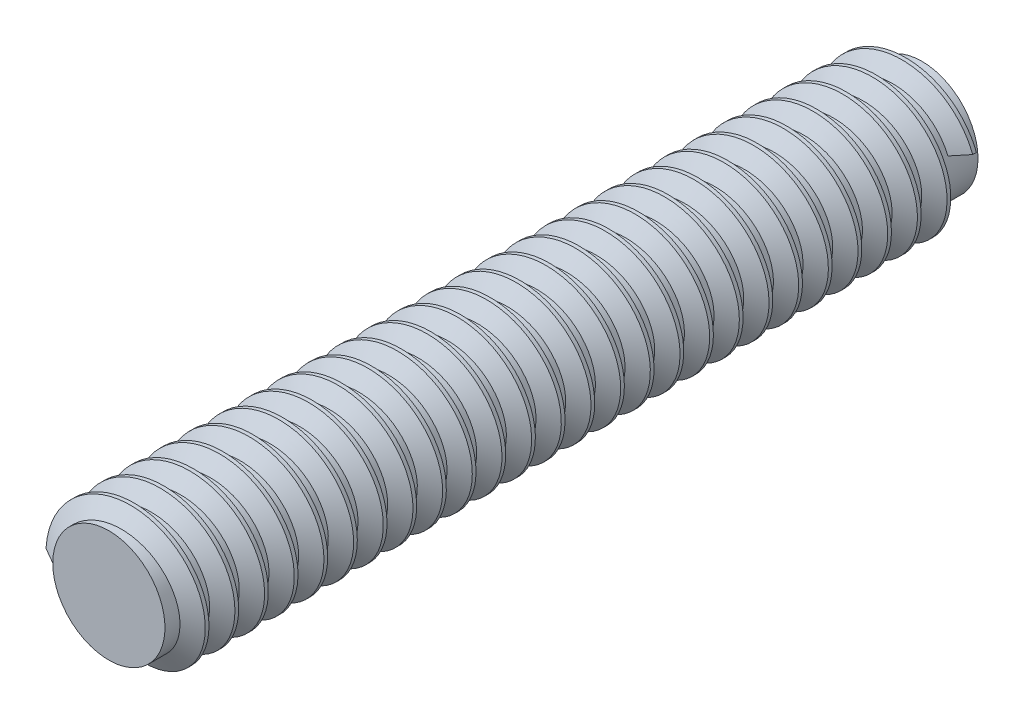
SolidWorks part; units mm, degrees
ref_plane "Front Plane" through (0, 0, 0) normal (0, 0, 1) x (1, 0, 0)
ref_plane "Top Plane" through (0, 0, 0) normal (0, 1, 0) x (1, 0, 0)
ref_plane "Right Plane" through (0, 0, 0) normal (1, 0, 0) x (0, 0, -1)
sketch "Sketch1" plane through (0, 0, 0) normal (0, 0, 1) x (1, 0, 0)
  circle A0 centre (0, 0) radius 2
  dimension "D1" = 4
extrude "Boss-Extrude1" add sketch "Sketch1" along normal blind 29
thread "Thread2" pitch 1.0583 method extrude profile "Thread Profile2" start angle 0, offset 0, length 28, pitch 1.0583, diameter 4
ref_plane "Plane2" through (-2, 0, 29) normal (0, -1, 0) x (-1, 0, 0)
sketch "Thread Profile2" plane through (-2, 0, 29) normal (0, -1, 0) x (-1, 0, 0)
  line L0 (0, 0) -> (0, 1.0583) construction
  line L1 (0, 0) -> (0.5728, 0.3307)
  line L2 (0.5728, 0.3307) -> (0.5728, 0.463)
  line L3 (0.5728, 0.463) -> (0, 0.7937)
  line L4 (0.5728, 0.3969) -> (0, 0.3969) construction
  line L11 (0, 0) -> (0, 0.7937)
  point P2 (0, 0)
  dimension "Pitch" = 1.0583
  dimension "Profile_Angle" = 60
  dimension "Profile_Land" = 0.1323
  dimension "Profile_Height" = 0.5728
